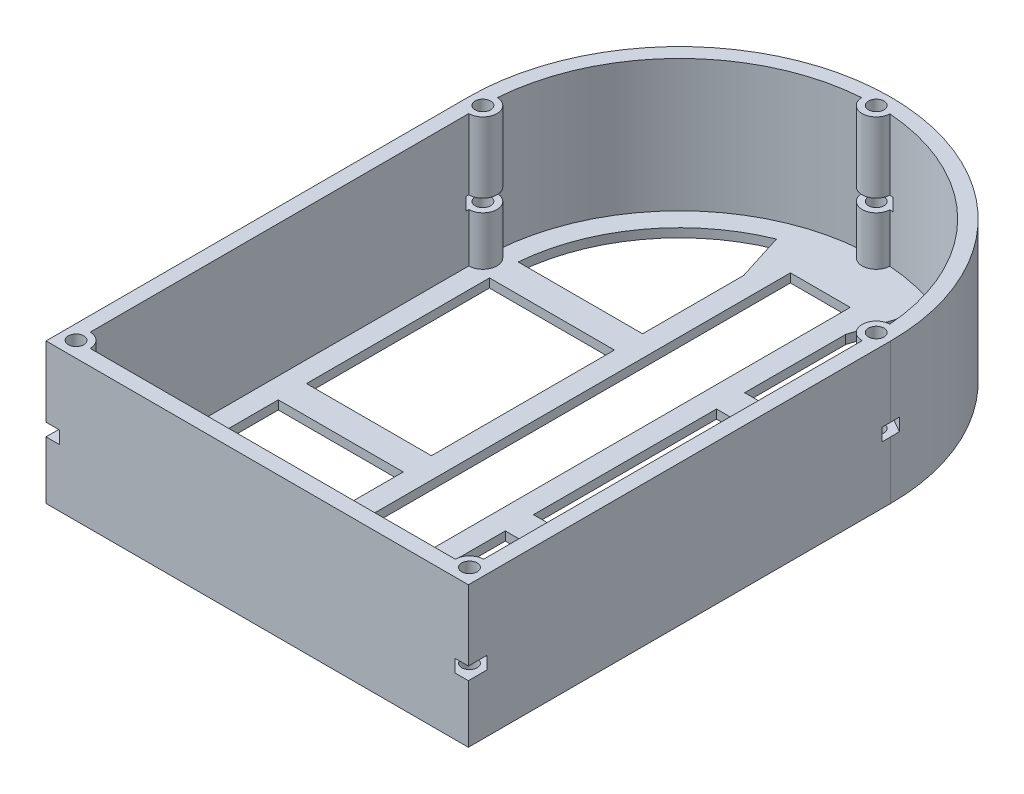
SolidWorks part; units mm, degrees
ref_plane "Front Plane" through (0, 0, 0) normal (0, 0, 1) x (1, 0, 0)
ref_plane "Top Plane" through (0, 0, 0) normal (0, 1, 0) x (1, 0, 0)
ref_plane "Right Plane" through (0, 0, 0) normal (1, 0, 0) x (0, 0, -1)
sketch "Sketch1" plane through (0, 0, 0) normal (0, 1, 0) x (1, 0, 0)
  line L1 (-30, 0) -> (30, 0) construction
  line L2 (-30, 0) -> (-30, -60)
  line L3 (-30, -60) -> (30, -60)
  line L4 (30, 0) -> (30, -60)
  line L5 (-30, 0) -> (30, -60) construction
  line L6 (-30, -60) -> (30, 0) construction
  line L9 (27.785, -57.785) -> (27.94, -57.785)
  line L10 (27.94, -55.785) -> (27.94, -2)
  line L11 (-25.94, -57.785) -> (25.94, -57.785)
  line L12 (-27.94, -2) -> (-27.94, -55.785)
  arc A0 (-30, 0) -> (30, 0) centre (0, 0) cw
  circle A1 centre (27.94, 0) radius 1.1
  circle A2 centre (-27.94, 0) radius 1.1
  circle A3 centre (0, 27.94) radius 1.1
  circle A4 centre (-27.94, -57.785) radius 1.1
  circle A5 centre (27.94, -57.785) radius 1.1
  arc A7 (27.8684, 1.9987) -> (27.94, -2) centre (27.94, 0) ccw
  arc A8 (27.94, -55.785) -> (25.94, -57.785) centre (27.94, -57.785) ccw
  arc A9 (-25.94, -57.785) -> (-27.94, -55.785) centre (-27.94, -57.785) ccw
  arc A11 (-1.9987, 27.8684) -> (1.9987, 27.8684) centre (0, 27.94) ccw
  circle A12 centre (0, 27.94) radius 2 construction
  circle A13 centre (27.94, 0) radius 2 construction
  arc A14 (1.9987, 27.8684) -> (27.8684, 1.9987) centre (0, 0) cw
  arc A15 (29.9391, -0.0609) -> (29.94, 0) centre (27.94, 0) ccw
  circle A16 centre (27.94, -57.785) radius 2 construction
  circle A17 centre (-27.94, -57.785) radius 2 construction
  arc A18 (-27.8684, 1.9987) -> (-1.9987, 27.8684) centre (0, 0) cw
  arc A19 (-27.94, -2) -> (-27.8684, 1.9987) centre (-27.94, 0) ccw
  point P0 (0, -30)
  dimension "D3" = 27.94
  dimension "D4" = 2.2
  dimension "D1" = 60
  dimension "D2" = 60
  dimension "D5" = 27.94
  dimension "D6" = 27.94
  dimension "D7" = 57.785
  dimension "D8" = 0.9
extrude "Boss-Extrude1" add sketch "Sketch1" against normal blind 20 contours A0 L2 L3 L4 A5 A4 A3 A2 A1 L12 A19 A18 A11 A14 A7 L10 A8 L11 A9 region at (0, 0, -29.8918)
sketch "Sketch2" plane through (0, -20, 0) normal (0, -1, 0) x (1, 0, 0)
  line L0 (-7.25, 53) -> (-7.25, 32)
  line L1 (-4.25, 50) -> (4.25, 50)
  line L2 (-4.25, 50) -> (-4.25, -20)
  line L3 (30, 0) -> (30, 60)
  line L4 (30, 60) -> (-30, 60)
  line L5 (-30, 60) -> (-30, 0)
  line L6 (30, 0) -> (30, 60)
  line L7 (30, 60) -> (-30, 60)
  line L8 (-30, 60) -> (-30, 0)
  line L9 (-4.25, -20) -> (4.25, -20)
  line L10 (4.25, 50) -> (4.25, -20)
  line L11 (-4.25, 50) -> (4.25, -20) construction
  line L12 (-4.25, -20) -> (4.25, 50) construction
  line L13 (-5.153, -23) -> (5.153, -23) construction
  line L14 (7.25, 53) -> (7.25, 32)
  line L16 (0, 0) -> (-7.5159, -23.8435) construction
  line L17 (25, 2) -> (25, 28)
  line L18 (0, 0) -> (7.5159, -23.8435) construction
  line L19 (25, 55) -> (7.25, 55)
  line L20 (-25, 55) -> (-25, 32)
  line L22 (-7.25, 53) -> (-7.25, 55)
  line L23 (5.153, -23) -> (5.5843, -24.3683) construction
  line L24 (-5.153, -23) -> (-5.5843, -24.3683) construction
  line L25 (-7.25, 53) -> (-7.25, -23) construction
  line L26 (-7.25, -23) -> (7.25, -23) construction
  line L27 (7.25, 53) -> (7.25, -23) construction
  line L28 (0, -6.6526) -> (-5.6084, -24.4448) construction
  line L29 (0, -6.6526) -> (5.6084, -24.4448) construction
  line L30 (-7.25, -16.3474) -> (-9.3993, -23.1658)
  line L31 (7.25, 53) -> (7.25, 55)
  line L32 (7.25, -16.3474) -> (9.3993, -23.1658)
  line L34 (-7.25, 55) -> (-25, 55)
  line L35 (25, 55) -> (-25, 55) construction
  line L36 (-7.25, 53) -> (7.25, 53) construction
  line L37 (-25, 0) -> (-7.25, 0) construction
  line L38 (25, 0) -> (7.25, 0) construction
  line L39 (7.25, 30) -> (25, 30) construction
  line L40 (-7.25, 30) -> (-25, 30) construction
  line L41 (-24.9199, -2) -> (-7.25, -2)
  line L42 (25, 2) -> (7.25, 2)
  line L43 (-7.25, 32) -> (-25, 32)
  line L44 (7.25, 28) -> (25, 28)
  line L45 (-25, 2) -> (-7.25, 2)
  line L46 (24.9199, -2) -> (7.25, -2)
  line L47 (-7.25, 28) -> (-25, 28)
  line L48 (7.25, 32) -> (25, 32)
  line L49 (7.25, 2) -> (7.25, 0) construction
  line L50 (7.25, -2) -> (7.25, -16.3474)
  line L51 (7.25, 0) -> (7.25, -2) construction
  line L52 (-7.25, 0) -> (-7.25, -2) construction
  line L53 (-7.25, -2) -> (-7.25, -16.3474)
  line L54 (-7.25, 2) -> (-7.25, 0) construction
  line L55 (-7.25, 32) -> (-7.25, 30) construction
  line L56 (-7.25, 28) -> (-7.25, 2)
  line L57 (-7.25, 30) -> (-7.25, 28) construction
  line L58 (7.25, 32) -> (7.25, 30) construction
  line L59 (7.25, 28) -> (7.25, 2)
  line L60 (7.25, 30) -> (7.25, 28) construction
  line L61 (-25, 32) -> (-25, 30) construction
  line L62 (-25, 28) -> (-25, 2)
  line L63 (-25, 55) -> (-25, 0) construction
  line L64 (-25, 30) -> (-25, 28) construction
  line L65 (25, 30) -> (25, 32) construction
  line L66 (25, 32) -> (25, 55)
  line L67 (25, 0) -> (25, 55) construction
  line L68 (25, 28) -> (25, 30) construction
  line L69 (25, 0) -> (25, 2) construction
  line L70 (-25, 2) -> (-25, 0) construction
  line L71 (9.3993, -23.1658) -> (9.4234, -23.2422) construction
  line L72 (-9.3993, -23.1658) -> (-9.4234, -23.2422) construction
  line L73 (-25, -2) -> (-24.9199, -2) construction
  line L74 (-25, -2) -> (-7.25, -2) construction
  line L75 (25, -2) -> (24.9199, -2) construction
  line L76 (25, -2) -> (7.25, -2) construction
  arc A0 (-24.9199, -2) -> (-9.3993, -23.1658) centre (0, 0) ccw
  arc A1 (-30, 0) -> (30, 0) centre (0, 0) ccw
  arc A2 (-30, 0) -> (30, 0) centre (0, 0) ccw
  arc A3 (-5.5843, -24.3683) -> (5.5843, -24.3683) centre (0, 0) ccw construction
  arc A4 (-25, 0) -> (25, 0) centre (0, 0) ccw construction
  arc A5 (9.3993, -23.1658) -> (24.9199, -2) centre (0, 0) ccw
  arc A6 (24.9199, -2) -> (25, 0) centre (0, 0) ccw construction
  arc A7 (-25, 0) -> (-24.9199, -2) centre (0, 0) ccw construction
  point P0 (0, 15)
  point P43 (25, 27.5)
  dimension "D2" = 8.5
  dimension "D3" = 70
  dimension "D4" = 15
  dimension "D7" = 30
  dimension "D1" = 0
  dimension "D5" = 3
  dimension "D6" = 5
  dimension "D8" = 2
  dimension "D9" = 2
  dimension "D10" = 2
extrude "Boss-Extrude2" add sketch "Sketch2" against normal blind 1.25
sketch "Sketch3" plane through (0, 0, 0) normal (0, 1, 0) x (1, 0, 0)
  line L0 (-30, -60) -> (30, -60) construction
  line L1 (2.4249, 27.94) -> (1.2124, 30.04)
  line L2 (1.2124, 30.04) -> (-1.2124, 30.04)
  line L3 (-1.2124, 30.04) -> (-2.4249, 27.94)
  line L4 (-1.8187, 26.89) -> (-1.2124, 25.84) construction
  line L5 (-1.2124, 25.84) -> (1.2124, 25.84)
  line L6 (1.8187, 26.89) -> (2.4249, 27.94) construction
  line L7 (27.94, -2.4249) -> (30.04, -1.2124)
  line L8 (30.04, -1.2124) -> (30.04, 1.2124)
  line L9 (30.04, 1.2124) -> (27.94, 2.4249)
  line L10 (26.89, 1.8187) -> (25.84, 1.2124) construction
  line L11 (25.84, 1.2124) -> (25.84, -1.2124)
  line L12 (25.84, -1.2124) -> (27.94, -2.4249)
  line L13 (30.2822, -58.4126) -> (29.6546, -56.0704)
  line L14 (29.6546, -56.0704) -> (27.3124, -55.4428)
  line L15 (27.3124, -55.4428) -> (25.5978, -57.1574)
  line L16 (25.5978, -57.1574) -> (26.2254, -59.4996)
  line L17 (26.2254, -59.4996) -> (28.5676, -60.1272)
  line L18 (29.4249, -59.2699) -> (30.2822, -58.4126) construction
  line L19 (-25.5978, -57.1574) -> (-27.3124, -55.4428)
  line L20 (-27.3124, -55.4428) -> (-29.6546, -56.0704)
  line L21 (-29.6546, -56.0704) -> (-30.2822, -58.4126)
  line L22 (-29.4249, -59.2699) -> (-28.5676, -60.1272) construction
  line L23 (-28.5676, -60.1272) -> (-26.2254, -59.4996)
  line L24 (-26.2254, -59.4996) -> (-25.5978, -57.1574)
  line L25 (-30.04, 1.2124) -> (-30.04, -1.2124)
  line L26 (-30.04, -1.2124) -> (-27.94, -2.4249)
  line L27 (-27.94, -2.4249) -> (-25.84, -1.2124)
  line L28 (-25.84, -1.2124) -> (-25.84, 1.2124)
  line L29 (-25.84, 1.2124) -> (-26.89, 1.8187) construction
  line L30 (-27.94, 2.4249) -> (-30.04, 1.2124)
  line L31 (-30.2822, -58.4126) -> (-30.9098, -60.7548)
  line L32 (-30.9098, -60.7548) -> (-28.5676, -60.1272)
  line L33 (-30.2822, -58.4126) -> (-29.4249, -59.2699) construction
  line L34 (28.5676, -60.1272) -> (30.9098, -60.7548)
  line L35 (30.9098, -60.7548) -> (30.2822, -58.4126)
  line L36 (28.5676, -60.1272) -> (29.4249, -59.2699) construction
  line L37 (-27.94, 2.4249) -> (-27.4431, 2.7117)
  line L38 (-27.4431, 2.7117) -> (-25.84, 1.2124)
  line L39 (-26.89, 1.8187) -> (-27.94, 2.4249) construction
  line L40 (27.94, 2.4249) -> (27.2976, 2.7958)
  line L41 (27.2976, 2.7958) -> (25.84, 1.2124)
  line L42 (27.94, 2.4249) -> (26.89, 1.8187) construction
  line L43 (-2.4249, 27.94) -> (-2.9234, 27.0765)
  line L44 (-2.9234, 27.0765) -> (-1.2124, 25.84)
  line L45 (1.2124, 25.84) -> (2.6648, 27.5244)
  line L46 (2.6648, 27.5244) -> (2.4249, 27.94)
  line L47 (-2.4249, 27.94) -> (-1.8187, 26.89) construction
  line L48 (1.2124, 25.84) -> (1.8187, 26.89) construction
  circle A0 centre (0, 27.94) radius 2.1 construction
  circle A1 centre (27.94, 0) radius 2.1 construction
  circle A2 centre (27.94, -57.785) radius 2.1 construction
  circle A3 centre (-27.94, -57.785) radius 2.1 construction
  circle A4 centre (-27.94, 0) radius 2.1 construction
  dimension "D1" = 4.2
  dimension "D2" = 45
  dimension "D3" = 45
extrude "Cut-Extrude1" cut sketch "Sketch3" against normal blind 1.8 from offset 10 offset against normal yes
